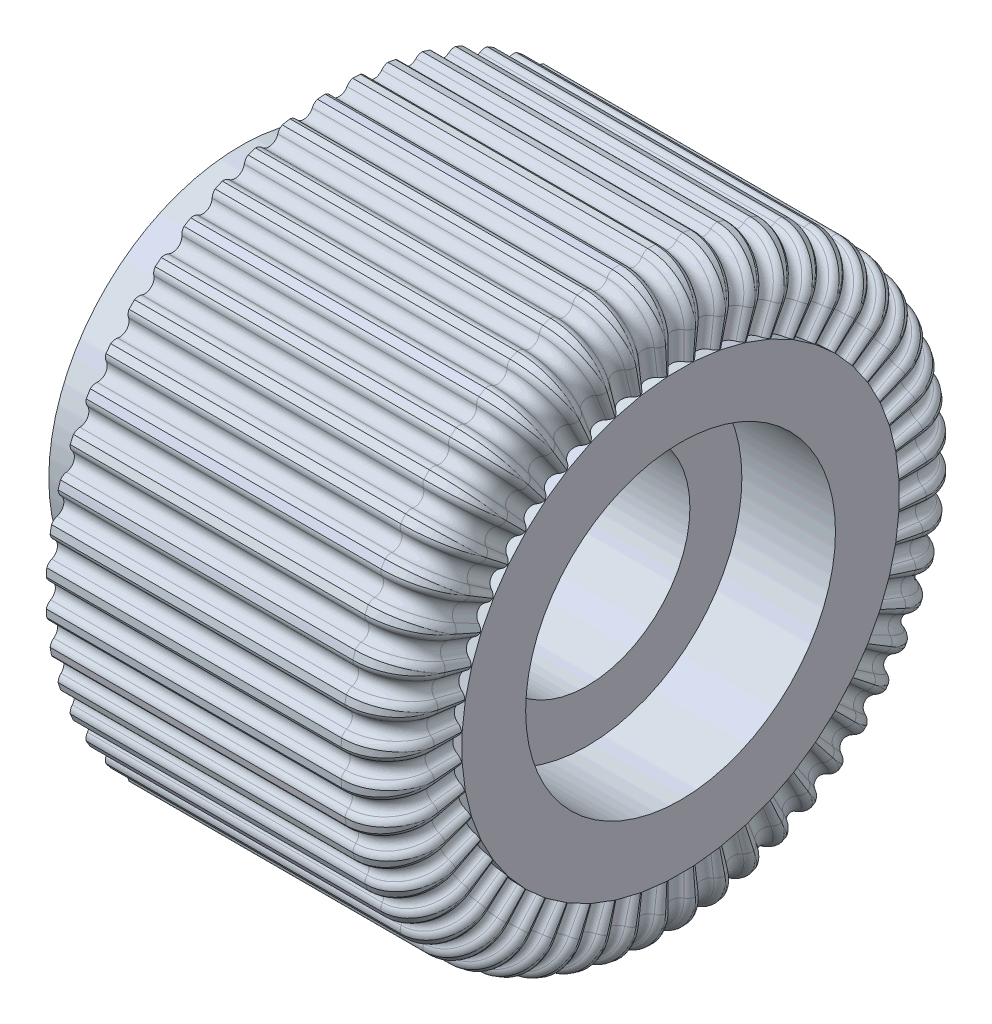
SolidWorks part; units mm, degrees
ref_plane "Plane1" through (0, 0, 0) normal (0, 0, 1) x (1, 0, 0)
ref_plane "Plane2" through (0, 0, 0) normal (0, 1, 0) x (1, 0, 0)
ref_plane "Plane3" through (0, 0, 0) normal (1, 0, 0) x (0, 0, -1)
sketch "Sketch1" plane through (0, 0, 0) normal (0, 0, 1) x (1, 0, 0)
  line L0 (0, 0) -> (11.938, 0) construction
  line L1 (0, 2.794) -> (0, 5.207)
  line L2 (0, 5.207) -> (4.826, 5.207)
  line L3 (4.826, 5.207) -> (4.826, 6.35)
  line L4 (4.826, 6.35) -> (2.667, 6.35)
  line L5 (2.667, 6.35) -> (2.667, 7.9502)
  line L6 (2.667, 7.9502) -> (10.668, 7.9502)
  line L7 (11.938, 6.6802) -> (11.938, 4.204)
  line L8 (11.938, 4.204) -> (9.398, 4.204)
  line L9 (9.398, 4.204) -> (9.398, 2.794)
  line L10 (9.398, 2.794) -> (0, 2.794)
  arc A0 (11.938, 6.6802) -> (10.668, 7.9502) centre (10.668, 6.6802) ccw
  dimension "D2" = 1.27
  dimension "D1" = 2.794
  dimension "D3" = 9.271
  dimension "D4" = 2.54
  dimension "D5" = 11.938
  dimension "D6" = 5.207
  dimension "D7" = 7.9502
  dimension "D8" = 4.204
  dimension "D9" = 1.6002
  dimension "D10" = 4.826
revolve "Base-Revolve" add sketch "Sketch1" angle 360 about L0
sketch "Sketch3" plane through (0, 0, 0) normal (0, 0, 1) x (1, 0, 0)
  line L1 (11.684, 6.6802) -> (11.684, 5.9273)
  line L2 (11.684, 6.6802) -> (11.684, -6.6802)
  line L3 (10.668, 7.6962) -> (2.667, 7.6962)
  line L4 (10.668, 7.9502) -> (2.667, 7.9502) construction
  line L5 (10.668, 7.6962) -> (2.667, 7.6962)
  arc A1 (11.684, 6.6802) -> (10.668, 7.6962) centre (10.668, 6.6802) ccw
  arc A2 (11.684, 6.6802) -> (10.668, 7.6962) centre (10.668, 6.6802) ccw
  dimension "D2" = 2.0229
  dimension "D1" = 0.254
ref_plane "Plane4" through (11.684, 5.9273, 0) normal (0, -1, 0) x (1, 0, 0)
sketch "Sketch4" plane through (11.684, 5.9273, 0) normal (0, -1, 0) x (1, 0, 0)
  line L0 (-11.684, 0) -> (0.254, 0) construction
  line L1 (0.254, -4.204) -> (0.254, 4.204) construction
  line L4 (0.254, -6.6802) -> (0.254, 6.6802) construction
  line L6 (0.254, 0.4399) -> (0.254, -0.4399)
  arc A0 (0.127, 0.22) -> (0.127, -0.22) centre (0.254, 0) ccw
  arc A1 (0.254, 0.4399) -> (0.127, 0.22) centre (0, 0.4399) cw
  arc A2 (0.254, -0.4399) -> (0.127, -0.22) centre (0, -0.4399) ccw
  dimension "D1" = 0.254
  dimension "D2" = 0.254
sweep "Cut-Sweep1" cut profiles "Sketch4" path "Sketch3"
pattern_circular "CirPattern1" count 52 every 6.923 about axis through (0, 0, 0) along (1, 0, 0) of "Cut-Sweep1"
